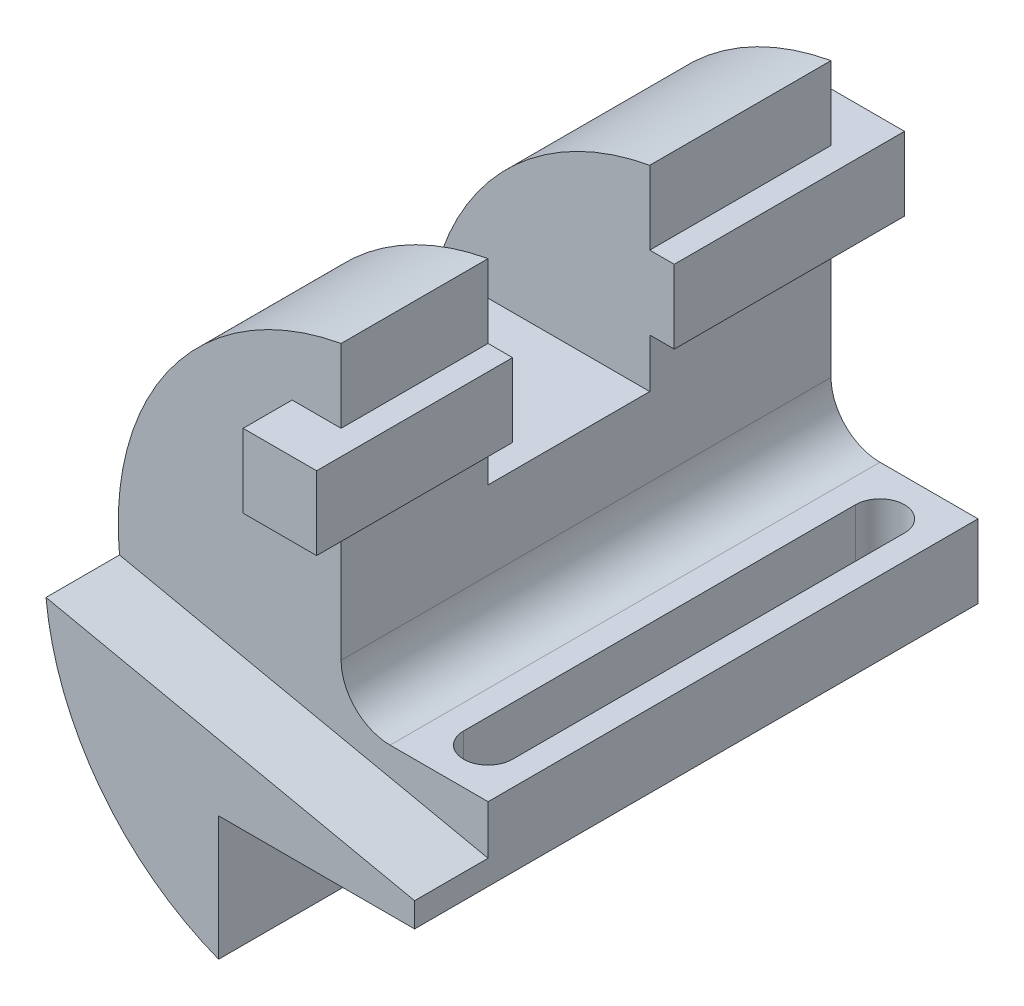
SolidWorks part; units mm, degrees
note: The reader was unsure of these and kept them because the rebuilt part matched: shared geometry of "Sketch1<5>".
material "1060 Alloy"
ref_plane "Front Plane" through (0, 0, 0) normal (0, 0, 1) x (1, 0, 0)
ref_plane "Top Plane" through (0, 0, 0) normal (0, 1, 0) x (1, 0, 0)
ref_plane "Right Plane" through (0, 0, 0) normal (1, 0, 0) x (0, 0, -1)
other "Center of Mass"
sketch "Sketch1" plane through (0, 0, 0) normal (0, 0, 1) x (1, 0, 0)
  line L5 (-178.4995, 0) -> (178.4995, 0) construction
  line L6 (0, -185.1274) -> (0, 185.1274) construction
  line L7 (-10, 106.3628) -> (-10, 50.3628)
  line L8 (0, 40.3628) -> (20, 40.3628)
  line L9 (20, 40.3628) -> (20, 25.3628)
  line L10 (20, 25.3628) -> (-20, 25.3628)
  line L11 (-20, 25.3628) -> (-20, 0)
  line L12 (-55.235, 46.3545) -> (20, 30.3628)
  line L13 (-5, 91.3628) -> (-20, 91.3628)
  line L14 (-5, 91.3628) -> (-5, 76.3628)
  line L15 (-5, 76.3628) -> (-20, 76.3628)
  line L16 (-20, 91.3628) -> (-20, 76.3628)
  arc A2 (-20, 0) -> (-10, 106.3628) centre (0, 51.7711) cw
  arc A3 (-10, 50.3628) -> (0, 40.3628) centre (0, 50.3628) ccw
  point P3 (0, 0)
  point P6 (0, 0)
  point P21 (-48.4413, 33.4385)
  point P22 (20, 16.1511)
  point P23 (-18.9487, 82.0658)
  point P24 (-18.9818, 84.4289)
  point P25 (-20, 66.1845)
  point P27 (-5, 81.0139)
  dimension "D1" = 10
  dimension "D5" = 10
  dimension "D2" = 55.5
  dimension "D3" = 20
  dimension "D4" = 40
  dimension "D6" = 5
  dimension "D7" = 15
  dimension "D8" = 78
  dimension "D9" = 5
  dimension "D10" = 15
  dimension "D11" = 66
  dimension "D12" = 15
  dimension "D13" = 15
extrude "Boss-Extrude1" add sketch "Sketch1" against normal blind 115 contours A3 L7 L15 L16 L13 A2 L12 L9 L8 | A2 L11 L10 L9 L12 | L13 L16 L15 L7
sketch "Sketch5" plane through (-10, 0, 0) normal (1, 0, 0) x (0, 0, -1)
  line L0 (115, 106.3628) -> (0, 106.3628) construction
  line L1 (30, 106.3628) -> (54.925, 106.3628)
  line L2 (30, 106.3628) -> (30, 59.7345)
  line L3 (30, 59.7345) -> (54.925, 59.7345)
  line L4 (54.925, 106.3628) -> (54.925, 59.7345)
  line L5 (0, 106.3628) -> (0, 50.3628) construction
  dimension "D1" = 30
extrude "Cut-Extrude1" cut sketch "Sketch1<5>" against normal blind 15 contours A3 L7 L15 L16 L13 A2 L12 L9 L8 | L13 L16 L15 L7
sketch "Sketch1<5>" plane through (0, 0, 0) normal (0, 0, 1) x (1, 0, 0) same geometry as "Sketch1"
ref_plane "Plane1" through (0, 0, -57.5) normal (0, 0, 1) x (1, 0, 0)
sketch "Sketch6" plane through (0, 0, -57.5) normal (0, 0, 1) x (1, 0, 0)
  line L0 (-5, 91.3628) -> (-20, 91.3628) construction
  line L1 (-5, 91.3628) -> (-5, 76.3628) construction
  line L2 (-20, 91.3628) -> (-20, 76.3628) construction
  line L3 (-5, 76.3628) -> (-20, 76.3628) construction
  line L4 (-5, 91.3628) -> (-20, 91.3628)
  line L5 (-5, 91.3628) -> (-5, 76.3628)
  line L6 (-20, 91.3628) -> (-20, 76.3628)
  line L7 (-5, 76.3628) -> (-20, 76.3628)
extrude "Boss-Extrude3" add sketch "Sketch6" along normal offset from surface 10 and the other way offset from surface (67.5 mm away) 10 up to face at (-8.1679, 53.4863, -15) offset beyond the face yes other way up to face at (-8.9039, 41.4129, -115)
sketch "Sketch7" plane through (-5, 0, 0) normal (1, 0, 0) x (0, 0, -1)
  line L0 (115, 106.3628) -> (15, 106.3628) construction
  line L1 (45, 106.3628) -> (78, 106.3628)
  line L2 (45, 106.3628) -> (45, 66.3628)
  line L3 (45, 66.3628) -> (78, 66.3628)
  line L4 (78, 106.3628) -> (78, 66.3628)
  line L5 (15, 76.3628) -> (15, 50.3628) construction
  line L6 (5, 76.3628) -> (125, 76.3628) construction
  dimension "D1" = 30
  dimension "D2" = 33
  dimension "D3" = 10
extrude "Cut-Extrude2" cut sketch "Sketch7" against normal up to surface (5 mm away)
sketch "Sketch8" plane through (0, 40.3628, 0) normal (0, 1, 0) x (1, 0, 0)
  line L0 (10, 25) -> (10, 105) construction
  line L1 (5, 25) -> (5, 105)
  line L2 (15, 25) -> (15, 105)
  line L3 (20, 115) -> (20, 15) construction
  line L5 (-55.235, 15) -> (20, 15) construction
  arc A0 (5, 25) -> (15, 25) centre (10, 25) ccw
  arc A1 (15, 105) -> (5, 105) centre (10, 105) ccw
  point P2 (10, 65)
  dimension "D1" = 80
  dimension "D2" = 10
  dimension "D3" = 10
  dimension "D4" = 10
extrude "Cut-Extrude3" cut sketch "Sketch8" against normal up to surface (15 mm away) up to face at (0, 25.3628, -57.5)
